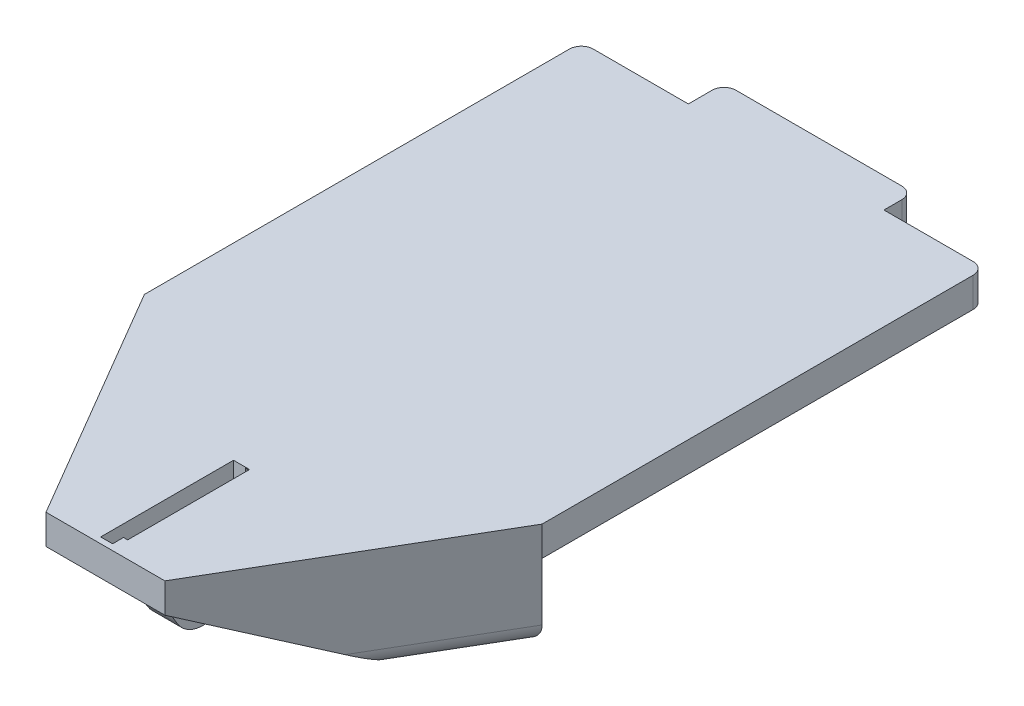
SolidWorks part; units mm, degrees
ref_plane "Front Plane" through (0, 0, 0) normal (0, 0, 1) x (1, 0, 0)
ref_plane "Top Plane" through (0, 0, 0) normal (0, 1, 0) x (1, 0, 0)
ref_plane "Right Plane" through (0, 0, 0) normal (1, 0, 0) x (0, 0, -1)
sketch "Sketch1" plane through (0, 0, 0) normal (0, 1, 0) x (1, 0, 0)
  line L0 (0, 0) -> (-16.35, 0)
  line L1 (-16.35, 0) -> (-16.35, -9.85)
  line L2 (-16.35, -9.85) -> (-2.6, -9.85)
  line L3 (-20.1, -33) -> (-20.1, -75)
  line L4 (-20.1, -75) -> (0, -75)
  line L5 (0, -75) -> (0, 0)
  line L6 (-2.6, -9.85) -> (-2.6, -33)
  line L7 (-2.6, -33) -> (-20.1, -33)
  dimension "D1" = 16.35
  dimension "D2" = 9.85
  dimension "D3" = 13.75
  dimension "D4" = 3.75
  dimension "D5" = 23.15
  dimension "D6" = 42
extrude "Boss-Extrude1" add sketch "Sketch1" along normal blind 7.7
sketch "Sketch2" plane through (0, 0, 75) normal (0, 0, 1) x (1, 0, 0)
  line L0 (-20.1, 7.7) -> (-20.1, 0) construction
  line L1 (-20.1, 5.1) -> (-13.1, 5.1)
  line L2 (-20.1, 5.1) -> (-20.1, 2)
  line L3 (-20.1, 2) -> (-13.1, 2)
  line L4 (-13.1, 5.1) -> (-13.1, 2)
  line L5 (-20.1, 0) -> (0, 0) construction
  dimension "D1" = 7
  dimension "D2" = 3.1
  dimension "D3" = 2
extrude "Cut-Extrude1" cut sketch "Sketch2" against normal through all
fillet "Fillet1" radius 10 1 edges at (-2.6, 3.85, 33)
sketch "Sketch3" plane through (0, 7.7, 0) normal (0, 1, 0) x (1, 0, 0)
  line L0 (0, 0) -> (0, -75)
  line L1 (0, -75) -> (-33.45, -75)
  line L2 (-33.45, -75) -> (-33.45, 0)
  line L3 (-33.45, 0) -> (0, 0)
  line L4 (0, -75) -> (0, -115)
  line L5 (0, -115) -> (-10, -115)
  line L6 (0, 0) -> (0, 4.5)
  line L7 (-33.45, -75) -> (-10, -115)
  line L8 (0, 4.5) -> (-33.45, 4.5)
  line L9 (-33.45, 4.5) -> (-33.45, 0)
  line M7 (0, -75) -> (0, 0)
  line M8 (0, 0) -> (-16.35, 0)
  line M9 (-16.35, 0) -> (-16.35, -9.85)
  line M10 (-16.35, -9.85) -> (-2.6, -9.85)
  line M11 (-2.6, -9.85) -> (-2.6, -23)
  arc M12 (-2.6, -23) -> (-12.6, -33) centre (-12.6, -23) cw
  line M13 (-12.6, -33) -> (-20.1, -33)
  line M14 (-20.1, -33) -> (-20.1, -75)
  line M15 (-20.1, -75) -> (0, -75)
  dimension "D1" = 33.45
  dimension "D2" = 40
  dimension "D3" = 10
  dimension "D4" = 4.5
extrude "Boss-Extrude2" add sketch "Sketch3" along normal blind 5 contours M15 M7 M8 M9 M10 M11 M12 M13 M14 | L3 L2 L1 M14 M13 M12 M11 M10 M9 | L5 L4 L1 M15 | L3 M8 region at (-9.1846, 7.7, 44.4658) region at (-16.725, 7.7, -2.25) region at (-11.9172, 7.7, 91.402) region at (-22.489, 7.7, 32.1752)
sketch "Sketch4" plane through (0, 0, 0) normal (1, 0, 0) x (0, 0, -1)
  line L0 (-115, 12.7) -> (-115, 15.7)
  line L1 (-115, 15.7) -> (-100, 15.7)
  line L2 (-100, 15.7) -> (-55.25, 12.7)
  line L3 (-115, 12.7) -> (4.5, 12.7) construction
  line L4 (-115, 12.7) -> (-55.25, 12.7)
  point P8 (-55.25, 12.7)
  dimension "D1" = 15
  dimension "D2" = 3
extrude "Boss-Extrude3" [suppressed] add sketch "Sketch4" against normal up to surface (33.45 mm away) up to face at (-33.45, 10.2, 35.25)
sketch "Sketch5" plane through (-33.45, 0, 0) normal (-1, 0, 0) x (0, 0, 1)
  line L0 (75, 7.7) -> (75, -5)
  line L1 (75, -5) -> (90, -5)
  line L2 (90, -5) -> (115, 7.7)
  line L3 (115, 7.7) -> (75, 7.7)
  line L4 (33, 0) -> (75, 0) construction
  dimension "D1" = 5
  dimension "D2" = 15
extrude "Boss-Extrude4" add sketch "Sketch5" against normal up to surface (33.45 mm away) up to face at (0, 7.025, 46.375)
sketch "Sketch6" plane through (0, 7.7, 0) normal (0, 1, 0) x (1, 0, 0)
  line L0 (-33.45, -75) -> (-10, -115)
  line L1 (-10, -115) -> (-33.45, -115)
  line L2 (-33.45, -115) -> (-33.45, -75)
  point P4 (-10, -105)
  point P8 (-33.45, -105)
extrude "Cut-Extrude2" cut sketch "Sketch6" against normal through all both and the other way through all
sketch "Sketch7" plane through (0, 0, 0) normal (1, 0, 0) x (0, 0, -1)
  line L0 (-75, 0) -> (-82, 0)
  line L1 (-82, 0) -> (-80, -5)
  line L2 (-90, -5) -> (-75, -5) construction
  line L3 (-80, -5) -> (-75, -5)
  line L4 (-75, -5) -> (-75, 0)
  dimension "D1" = 5
  dimension "D2" = 7
extrude "Cut-Extrude3" cut sketch "Sketch7" against normal blind 10
fillet "Fillet3" radius 1 2 edges at (-5, -5, 80) (-10, -5, 77.5)
fillet "Fillet4" [suppressed] radius 5
mirror "Mirror1" about plane through (0, 7.7, 75) normal (-1, 0, 0) of bodies 110
fillet "Fillet5" radius 3 2 edges at (-29.0531, -5, 82.5) (29.0531, -5, 82.5)
sketch "Sketch8" plane through (0, 12.7, 0) normal (0, 1, 0) x (1, 0, 0)
  line L0 (33.45, 4.5) -> (33.45, -0.5)
  line L1 (33.45, -75) -> (33.45, 4.5) construction
  line L2 (33.45, -0.5) -> (16.45, -0.5)
  line L3 (16.45, -0.5) -> (16.45, 4.5)
  line L4 (33.45, 4.5) -> (-33.45, 4.5) construction
  line L5 (16.45, 4.5) -> (33.45, 4.5)
  line L6 (0, 37.0905) -> (0, -37.0905) construction
  line L7 (-16.45, -0.5) -> (-16.45, 4.5) construction
  line L8 (-33.45, -0.5) -> (-16.45, -0.5) construction
  line L9 (-33.45, 4.5) -> (-33.45, -0.5) construction
  line L10 (-16.45, 4.5) -> (-33.45, 4.5) construction
  line L11 (-15.45, -1.5) -> (-15.45, 5.5)
  line L12 (-15.45, 5.5) -> (-34.45, 5.5)
  line L13 (-34.45, 5.5) -> (-34.45, -1.5)
  line L14 (-34.45, -1.5) -> (-15.45, -1.5)
  point P13 (0, 0)
  dimension "D1" = 5
  dimension "D2" = 17
  dimension "D3" = 1
extrude "Cut-Extrude4" cut sketch "Sketch8" against normal up to surface (12.7 mm away) up to face at (0, 0, 38.0857)
fillet "Fillet6" radius 2 2 edges at (-15.45, 10.2, -4.5) (-33.45, 10.2, 1.5)
fillet "Fillet7" radius 2 2 edges at (33.45, 10.2, 0.5) (16.45, 10.2, -4.5)
ref_plane "Plane1" through (0.2, 0, 0) normal (-1, 0, 0) x (0, 0, 1)
sketch "Sketch11" plane through (0.2, 0, 0) normal (-1, 0, 0) x (0, 0, 1)
  line L0 (82.4909, -2.3) -> (93.4909, 15.7)
  line L1 (82.4909, -2.3) -> (103, -2.3)
  line L2 (93.4909, 15.7) -> (114, 15.7)
  line L3 (103, -2.3) -> (114, 15.7)
  line L4 (75, 12.7) -> (115, 12.7) construction
  line L5 (115, 12.7) -> (115, 7.7) construction
  circle A0 centre (103, -2.3) radius 1
  circle A1 centre (82.4909, -2.3) radius 1
  dimension "D6" = 2
  dimension "D7" = 2
  dimension "D1" = 18
  dimension "D2" = 17.5
  dimension "D3" = 11
  dimension "D4" = 3
  dimension "D5" = 1
sketch "Sketch12" plane through (0.2, 0, 0) normal (-1, 0, 0) x (0, 0, 1)
  line L2 (91.378, -4.3) -> (109.859, 5.0884)
  line L3 (95.9055, -2) -> (115, 7.7) construction
  line L4 (104.1217, -4.3) -> (115.7066, 14.6571)
  line L5 (82.4909, -4.3) -> (104.1217, -4.3)
  line L6 (104.1217, -4.3) -> (109.859, 5.0884)
  line L7 (91.378, -4.3) -> (104.1217, -4.3)
  line L8 (90, -5) -> (95.9055, -2) construction
  dimension "D1" = 2
extrude "Boss-Extrude5" add sketch "Sketch12" along normal mid plane 5
fillet "Fillet8" radius 5 1 edges at (0.2, -4.3, 104.1217)
extrude "Cut-Extrude5" cut sketch "Sketch11" against normal blind 0.7 contours A1 L1 A0 L3 L2 L0 | L0 A1 L1 | L1 A1 L0 | L3 A0 L1 | L1 A0 L3 region at (0.2, -2.3606, 82.3828) region at (0.2, -1.9879, 83.0474) region at (0.2, 6.7366, 98.2537) region at (0.2, -1.8214, 102.7316) region at (0.2, -2.5436, 103.1366)
sketch "Sketch13" plane through (0.2, 0, 0) normal (-1, 0, 0) x (0, 0, 1)
  line L0 (75, 12.7) -> (115, 12.7) construction
  line L1 (114, 12.7) -> (91.6576, 12.7)
  line L2 (114, 12.7) -> (114, 8.7)
  line L3 (114, 8.7) -> (91.6576, 8.7)
  line L4 (91.6576, 12.7) -> (91.6576, 8.7)
  line L5 (82.4909, -2.3) -> (93.4909, 15.7) construction
  point P8 (0, 0)
  point P9 (0, 0)
  point P11 (0, 0)
  dimension "D1" = 4
extrude "Cut-Extrude6" cut sketch "Sketch13" along normal blind 2
